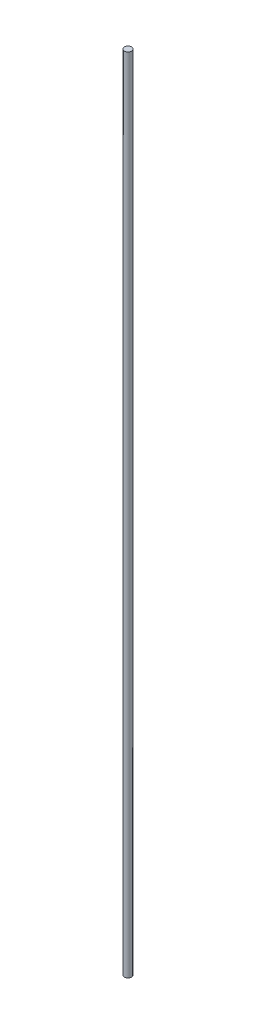
SolidWorks part; units mm, degrees
ref_plane "Front Plane" through (0, 0, 0) normal (0, 0, 1) x (1, 0, 0)
ref_plane "Top Plane" through (0, 0, 0) normal (0, 1, 0) x (1, 0, 0)
ref_plane "Right Plane" through (0, 0, 0) normal (1, 0, 0) x (0, 0, -1)
sketch "Sketch1" plane through (0, 0, 0) normal (0, 1, 0) x (1, 0, 0)
  circle A0 centre (0, 0) radius 1.397
  dimension "D1" = 2.794
extrude "Boss-Extrude1" add sketch "Sketch1" along normal blind 304.8
